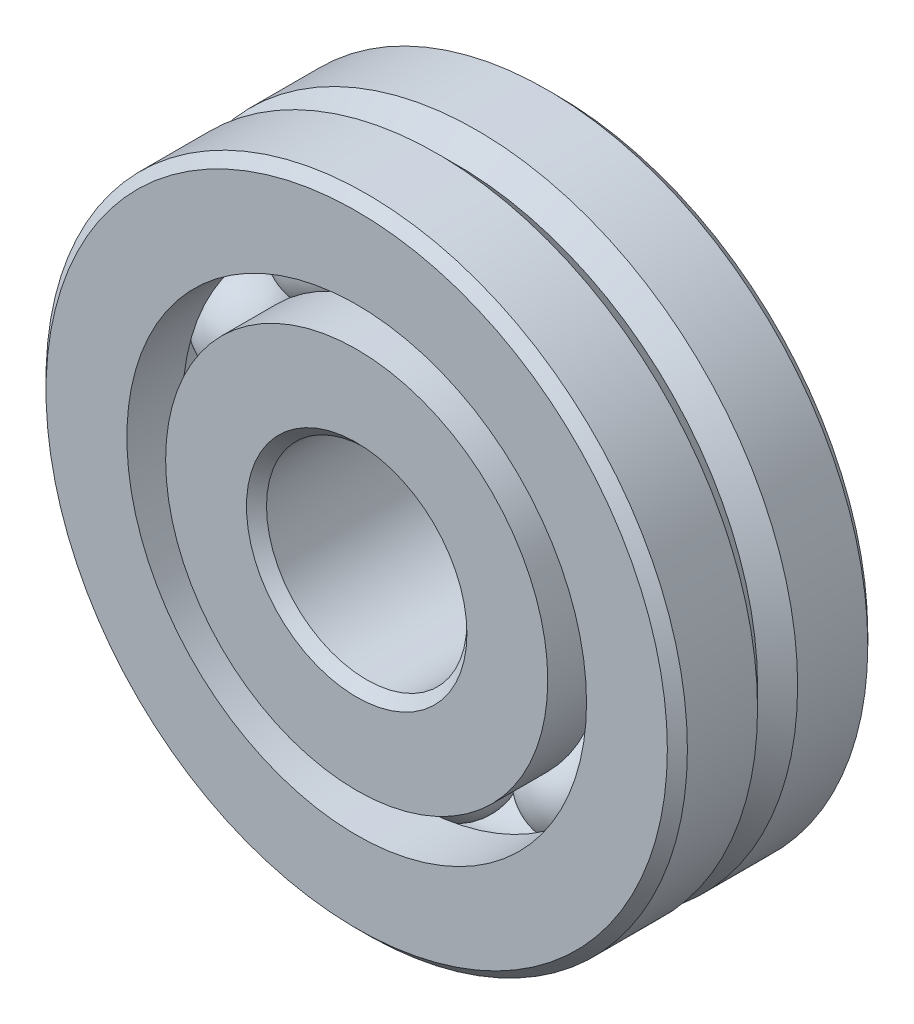
SolidWorks part; units mm, degrees
ref_plane "Front Plane" through (0, 0, 0) normal (0, 0, 1) x (1, 0, 0)
ref_plane "Top Plane" through (0, 0, 0) normal (0, 1, 0) x (1, 0, 0)
ref_plane "Right Plane" through (0, 0, 0) normal (1, 0, 0) x (0, 0, -1)
sketch "Sketch1" plane through (0, 0, 0) normal (1, 0, 0) x (0, 0, -1)
  line L0 (-2.5, 0) -> (2.5, 0) construction
  line L1 (0, 8) -> (0, -8) construction
  line L2 (2.25, 8) -> (0.5, 8)
  line L3 (-2.25, 8) -> (-2.5, 7.75)
  line L4 (-2.5, 7.75) -> (-2.5, 5.7335)
  line L5 (-2.5, 5.7335) -> (-1.1111, 5.7335)
  line L6 (2.5, 5.7335) -> (1.1111, 5.7335)
  line L7 (2.5, 7.75) -> (2.5, 5.7335)
  line L8 (2.25, 8) -> (2.5, 7.75)
  line L9 (0, 8) -> (0, 5.25) construction
  line L10 (0, 5.25) -> (0, 2.5) construction
  line L11 (0.5, 8) -> (0, 7.5)
  line L12 (0, 7.5) -> (-0.5, 8)
  line L13 (-0.5, 8) -> (-2.25, 8)
  arc A0 (-1.1111, 5.7335) -> (1.1111, 5.7335) centre (0, 5.25) cw
  point P14 (0, 2.5)
  point P15 (-0.5, 8)
  point P17 (0.5, 8)
  point P18 (0, 0)
  dimension "Width" = 5
  dimension "OD" = 16
  dimension "D1" = 45
  dimension "D2" = 0.25
  dimension "Shaft Dia" = 5
  dimension "D3" = 2.2222
  dimension "D4" = 0.4835
  dimension "D5" = 0.5
  dimension "D6" = 0.5
revolve "Revolve1" add sketch "Sketch1" angle 360 about L0
sketch "Sketch3" plane through (0, 0, 0) normal (1, 0, 0) x (0, 0, -1)
  line L0 (-2.5, 4.7665) -> (-1.1111, 4.7665)
  line L1 (0, 8) -> (0, -8) construction
  line L2 (-2.5, 7.75) -> (-2.5, 5.7335) construction
  line L3 (-2.5, 4.7665) -> (-2.5, 2.75)
  line L4 (-2.25, 8) -> (-2.5, 7.75) construction
  line L5 (-2.5, 2.75) -> (-2.25, 2.5)
  line L6 (-2.25, 2.5) -> (2.25, 2.5)
  line L7 (2.25, 8) -> (2.25, -8) construction
  line L8 (2.25, 2.5) -> (2.5, 2.75)
  line L9 (2.5, -7.75) -> (2.5, 7.75) construction
  line L10 (2.5, 2.75) -> (2.5, 4.7665)
  line L11 (2.5, 4.7665) -> (1.1111, 4.7665)
  line L13 (2.25, 8) -> (2.5, 7.75) construction
  arc A0 (1.1111, 5.7335) -> (-1.1111, 5.7335) centre (0, 5.25) ccw construction
  arc A1 (1.1111, 4.7665) -> (-1.1111, 4.7665) centre (0, 5.25) cw
revolve "Revolve3" add sketch "Sketch3" angle 360 about L0
sketch "Sketch4" plane through (0, 0, 0) normal (1, 0, 0) x (0, 0, -1)
  line L0 (-1.2118, 5.25) -> (1.2118, 5.25)
  arc A2 (-1.2118, 5.25) -> (1.2118, 5.25) centre (0, 5.25) cw
  arc A3 (1.1111, 5.7335) -> (-1.1111, 5.7335) centre (0, 5.25) ccw construction
revolve "Revolve4" add sketch "Sketch4" angle 360 about L0
ref_axis "Axis1" through (0, 0, -2.5) along (0, 0, 1)
pattern_circular "CirPattern1" count 10 over 360 about axis through (0, 0, -2.5) along (0, 0, 1) of bodies 104
sketch "Sketch5" plane through (0, 0, 0) normal (1, 0, 0) x (0, 0, -1)
  line L0 (-2.5, 5.7335) -> (-1.1111, 5.7335) construction
  line L1 (-2.375, 5.7335) -> (-1.2118, 5.7335)
  line L2 (-2.375, 5.7335) -> (-2.375, 4.7665)
  line L3 (-2.375, 4.7665) -> (-1.2118, 4.7665)
  line L4 (-1.2118, 5.7335) -> (-1.2118, 4.7665)
  line L5 (-2.5, 4.7665) -> (-1.1111, 4.7665) construction
  line L6 (2.5, 5.7335) -> (1.1111, 5.7335) construction
  line L7 (2.375, 5.7335) -> (1.2118, 5.7335)
  line L8 (2.375, 5.7335) -> (2.375, 4.7665)
  line L9 (2.375, 4.7665) -> (1.2118, 4.7665)
  line L10 (1.2118, 5.7335) -> (1.2118, 4.7665)
  line L11 (2.5, 4.7665) -> (1.1111, 4.7665) construction
  line L12 (-2.25, 8) -> (-2.5, 7.75) construction
  point P18 (-2.375, 7.875)
revolve "Revolve5" [suppressed] add sketch "Sketch5" angle 360 about L0
equation "\"D2@Sketch1\" = \"Width@Sketch1\"*.05"
equation "\"D3@Sketch1\" = \"Width@Sketch1\"/2.25"
equation "\"D4@Sketch1\" = (((\"OD@Sketch1\"-\"Width@Sketch1\")/2)/3.25)/3.5"
equation "\"D2@CirPattern1\" = 360/\"Balls@CirPattern1\""
